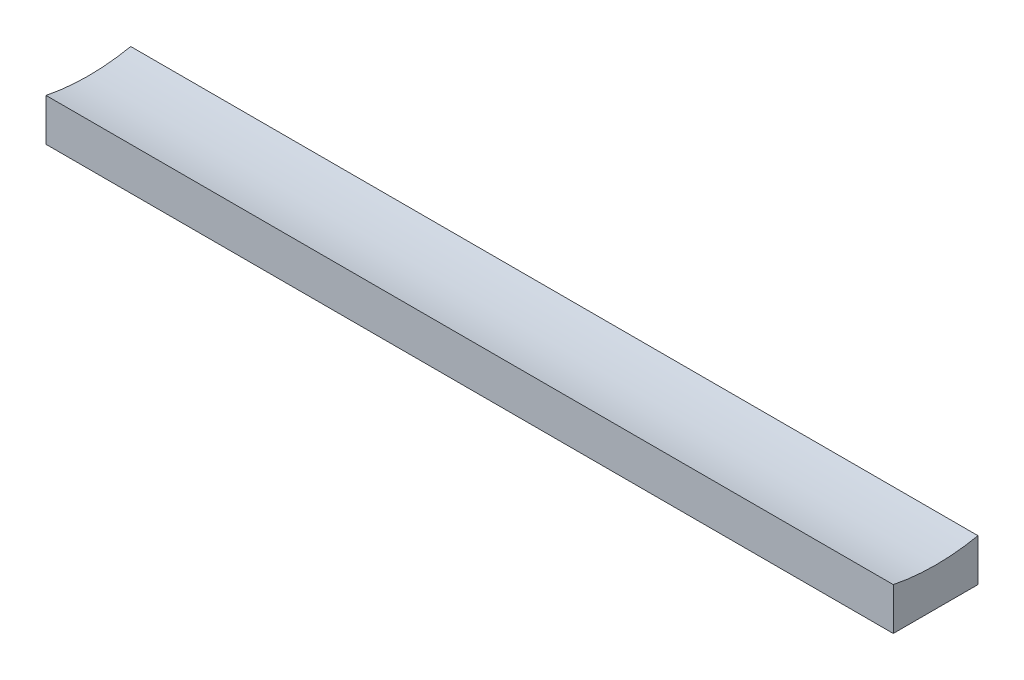
SolidWorks part; units mm, degrees
ref_plane "Front Plane" through (0, 0, 0) normal (0, 0, 1) x (1, 0, 0)
ref_plane "Top Plane" through (0, 0, 0) normal (0, 1, 0) x (1, 0, 0)
ref_plane "Right Plane" through (0, 0, 0) normal (1, 0, 0) x (0, 0, -1)
sketch "Face Sketch" plane through (0, 0, 0) normal (0, 1, 0) x (1, 0, 0)
  line L1 (-100, -10) -> (100, -10)
  line L2 (-100, -10) -> (-100, 10)
  line L3 (-100, 10) -> (100, 10)
  line L4 (100, -10) -> (100, 10)
  line L5 (-100, -10) -> (100, 10) construction
  line L6 (-100, 10) -> (100, -10) construction
  point P0 (0, 0)
  dimension "D1" = 20
  dimension "D2" = 200
extrude "Face Extrude" add sketch "Face Sketch" along normal blind 10
sketch "Profile Sketch" plane through (100, 0, 0) normal (1, 0, 0) x (0, 0, -1)
  circle A0 centre (0, 58.9898) radius 50
  dimension "D1" = 100
extrude "Profile Cut" cut sketch "Profile Sketch" against normal up to surface (200 mm away) up to face at (-100, 5, 0)
sketch "Angle Sketch" plane through (100, 0, 0) normal (1, 0, 0) x (0, 0, -1)
  line L0 (0, 0) -> (0, 8.9898) construction
  line L1 (-10, 0) -> (10, 0) construction
  arc A0 (-10, 10) -> (10, 10) centre (0, 58.9898) ccw construction
